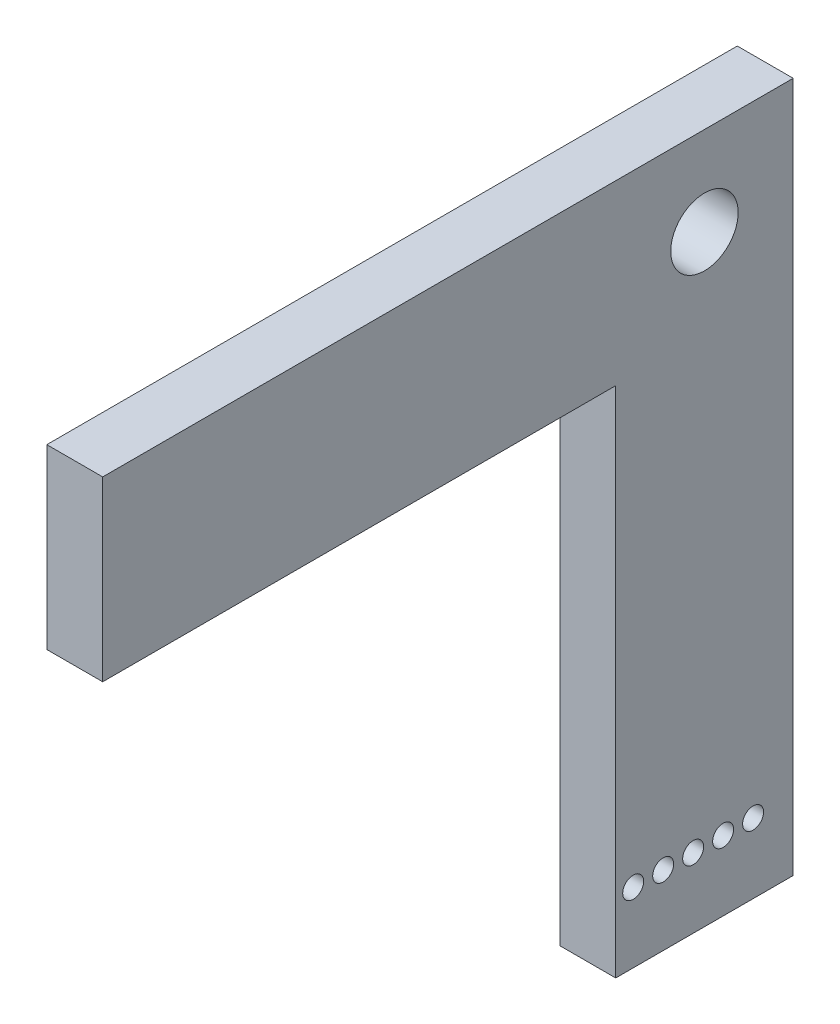
SolidWorks part; units mm, degrees
material "Hardboard"
ref_plane "Front Plane" through (0, 0, 0) normal (0, 0, 1) x (1, 0, 0)
ref_plane "Top Plane" through (0, 0, 0) normal (0, 1, 0) x (1, 0, 0)
ref_plane "Right Plane" through (0, 0, 0) normal (1, 0, 0) x (0, 0, -1)
sketch "Sketch1" plane through (0, 0, 0) normal (1, 0, 0) x (0, 0, -1)
  line L0 (-43.0661, 6.35) -> (6.35, 6.35)
  line L1 (6.35, 6.35) -> (6.35, -43.0661)
  line L2 (6.35, -43.0661) -> (-6.35, -43.0661)
  line L3 (-6.35, -43.0661) -> (-6.35, -6.35)
  line L4 (-6.35, -6.35) -> (-43.0661, -6.35)
  line L5 (-43.0661, -6.35) -> (-43.0661, 6.35)
  line L6 (-6.35, -6.35) -> (6.35, 6.35) construction
  circle A0 centre (0, 0) radius 2.413
  circle A1 centre (-5.1, -38.0661) radius 0.75
  circle A2 centre (-2.9545, -38.0661) radius 0.75
  circle A3 centre (-0.8091, -38.0661) radius 0.75
  circle A4 centre (1.3364, -38.0661) radius 0.75
  circle A5 centre (3.4818, -38.0661) radius 0.75
  dimension "D1" = 4.826
  dimension "D2" = 1.5
  dimension "D3" = 1.25
  dimension "D4" = 5
  dimension "D5" = 5
extrude "Boss-Extrude1" add sketch "Sketch1" along normal mid plane 4
